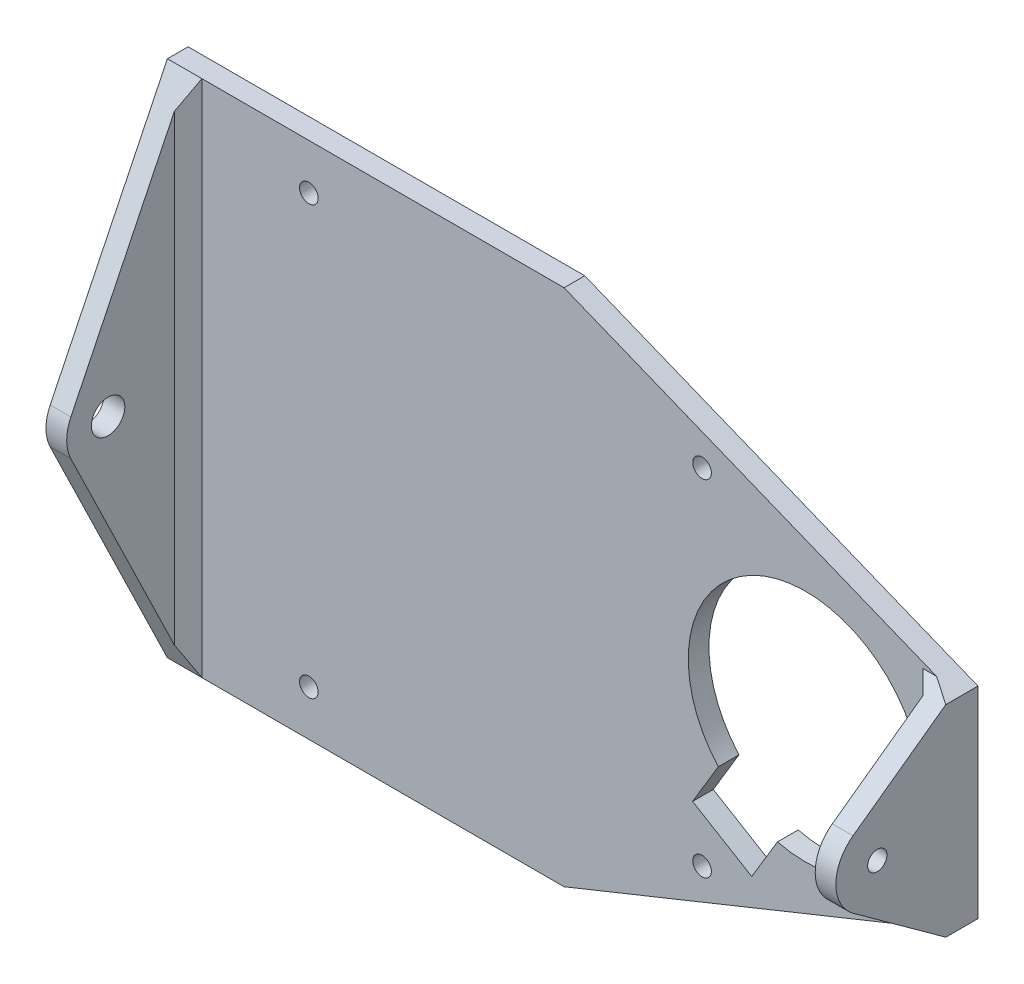
SolidWorks part; units mm, degrees
material "PET 90%"
ref_plane "Front Plane" through (0, 0, 0) normal (0, 0, 1) x (1, 0, 0)
ref_plane "Top Plane" through (0, 0, 0) normal (0, 1, 0) x (1, 0, 0)
ref_plane "Right Plane" through (0, 0, 0) normal (1, 0, 0) x (0, 0, -1)
sketch "Sketch1" plane through (0, 0, 0) normal (0, 0, 1) x (1, 0, 0)
  line L0 (-42.5, 37.6) -> (-42.5, -37.6)
  line L1 (-42.5, -37.6) -> (72, -37.6)
  line L2 (72, -37.6) -> (72, 37.6)
  line L3 (72, 37.6) -> (-42.5, 37.6)
  line L4 (0, 0) -> (-35.5, 0) construction
  line L5 (-35.5, 0) -> (-42.5, 0) construction
  line L6 (0, 0) -> (66, 0) construction
  line L7 (66, 0) -> (72, 0) construction
  line L8 (-22, 31) -> (-22, 32.6) construction
  line L9 (-22, 32.6) -> (-22, 37.6) construction
  line L10 (45.4594, -15.3422) -> (41.858, -21.3447) construction
  line L11 (34.998, -17.2287) -> (38.5995, -11.2262) construction
  line L12 (41.858, -21.3447) -> (34.998, -17.2287) construction
  line L13 (45.4594, -15.3422) -> (41.858, -21.3447) construction
  line L14 (34.998, -17.2287) -> (38.5995, -11.2262) construction
  line L15 (41.858, -21.3447) -> (34.998, -17.2287) construction
  circle A0 centre (-22, 31) radius 1.6 construction
  circle A1 centre (35, 25) radius 1.6 construction
  circle A2 centre (35, -25) radius 1.6 construction
  circle A3 centre (-22, -31) radius 1.6 construction
  circle A4 centre (-22, 31) radius 1.6 construction
  circle A5 centre (35, 25) radius 1.6 construction
  circle A6 centre (35, -25) radius 1.6 construction
  circle A7 centre (-22, -31) radius 1.6 construction
  arc A8 (-25.36, 24.8419) -> (-25.36, -24.8419) centre (0, 0) ccw construction
  arc A9 (-25.36, 24.8419) -> (-25.36, -24.8419) centre (0, 0) ccw construction
  arc A14 (45.4594, -15.3422) -> (38.5995, -11.2262) centre (50, 0) ccw construction
  arc A15 (45.4594, -15.3422) -> (38.5995, -11.2262) centre (50, 0) ccw construction
  dimension "D1" = 7
  dimension "D3" = 5
  dimension "D2" = 6
extrude "Boss-Extrude1" add sketch "Sketch1" along normal blind 3
ref_plane "Plane1" through (0, 0, 14.6) normal (0, 0, 1) x (1, 0, 0)
sketch "Sketch3" plane through (0, 0, 0) normal (0, 0, 1) x (1, 0, 0)
  line L0 (38.428, -19.2867) -> (50, 0) construction
  line L1 (41.858, -21.3447) -> (34.998, -17.2287) construction
  line L2 (37.353, -11.3601) -> (33.626, -17.5717)
  line L3 (33.626, -17.5717) -> (42.201, -22.7166)
  line L4 (42.201, -22.7166) -> (45.9279, -16.5051)
  line L5 (34.998, -17.2287) -> (38.5995, -11.2262) construction
  line L6 (15, -37.6) -> (72, -14.6)
  line L7 (45.4594, -15.3422) -> (41.858, -21.3447) construction
  line L8 (-42.5, -37.6) -> (72, -37.6) construction
  line L9 (72, -37.6) -> (72, 37.6) construction
  line L10 (15, 37.6) -> (72, 14.6)
  line L11 (72, 37.6) -> (-42.5, 37.6) construction
  line L12 (0, 0) -> (-42.5, 0) construction
  line L13 (-42.5, 37.6) -> (-42.5, -37.6) construction
  line L14 (15, -37.6) -> (72, -37.6)
  line L15 (72, -37.6) -> (72, -14.6)
  line L16 (72, 37.6) -> (15, 37.6)
  line L17 (72, 14.6) -> (72, 37.6)
  arc A2 (45.9279, -16.5051) -> (37.353, -11.3601) centre (50, 0) ccw
  arc A3 (45.4594, -15.3422) -> (38.5995, -11.2262) centre (50, 0) ccw construction
  circle A5 centre (35, 25) radius 1.35
  circle A6 centre (-22, 31) radius 1.35
  circle A7 centre (-22, -31) radius 1.35
  circle A8 centre (35, -25) radius 1.35
  dimension "D1" = 1
  dimension "D4" = 2.7
  dimension "D2" = 1
  dimension "D3" = 1
  dimension "D5" = 57
  dimension "D6" = 23
extrude "Cut-Extrude1" cut sketch "Sketch3" along normal up to next
sketch "Sketch5" plane through (0, 0, 3) normal (0, 0, 1) x (1, 0, 0)
  line L0 (72, -14.6) -> (15, -37.6) construction
  line L1 (72, -14.6) -> (69, -15.8105)
  line L2 (72, -14.6) -> (72, 14.6) construction
  line L3 (72, -14.6) -> (72, 14.6)
  line L4 (15, 37.6) -> (72, 14.6) construction
  line L5 (69, 15.8105) -> (72, 14.6)
  line L6 (69, 15.8105) -> (69, -15.8105)
  line L7 (-42.5, 37.6) -> (-42.5, -37.6) construction
  line L8 (-42.5, 37.6) -> (-42.5, -37.6)
  line L9 (-39.5, 37.6) -> (-39.5, -37.6)
  line L10 (15, 37.6) -> (-42.5, 37.6) construction
  line L11 (-42.5, -37.6) -> (15, -37.6) construction
  line L12 (-42.5, -37.6) -> (-39.5, -37.6)
  line L13 (-39.5, 37.6) -> (-42.5, 37.6)
  dimension "D1" = 3
  dimension "D2" = 3
extrude "Boss-Extrude3" add sketch "Sketch5" along normal offset from surface (17.6 mm away) 6 up to plane "Plane1" offset beyond the face yes
ref_axis "Rotation" through (-22.5499, 0, 14.6) along (1, 0, 0)
sketch "Sketch6" plane through (-42.5, 0, 0) normal (-1, 0, 0) x (0, 0, 1)
  line L1 (20.6, 37.6) -> (20.6, -37.6) construction
  line L2 (3, 37.6) -> (19.9966, 2.6224)
  line L5 (20.6, 37.6) -> (20.6, 0)
  line L8 (0, 0) -> (20.6, 0) construction
  line L9 (3, 37.6) -> (0, 37.6) construction
  line L10 (3, 37.6) -> (0, 37.6) construction
  line L11 (20.6, 37.6) -> (3, 37.6)
  arc A0 (20.6, 0) -> (19.9966, 2.6224) centre (14.6, 0) ccw
extrude "Cut-Extrude2" cut sketch "Sketch6" against normal up to next
sketch "Sketch7" plane through (-42.5, 0, 0) normal (-1, 0, 0) x (0, 0, 1)
  line L1 (20.6, 0) -> (20.6, -37.6)
  line L2 (19.9966, -2.6224) -> (3, -37.6)
  line L5 (3, -37.6) -> (0, -37.6) construction
  line L6 (3, -37.6) -> (0, -37.6) construction
  line L7 (20.6, -37.6) -> (3, -37.6)
  arc A0 (19.9966, -2.6224) -> (20.6, 0) centre (14.6, 0) ccw
extrude "Cut-Extrude3" cut sketch "Sketch7" against normal up to next
sketch "Sketch8" plane through (69, 0, 0) normal (-1, 0, 0) x (0, 0, 1)
  line L0 (18.1196, 4.8593) -> (3, 15.8105)
  line L1 (20.6, 15.8105) -> (3, 15.8105) construction
  line L2 (20.6, 15.8105) -> (3, 15.8105)
  line L4 (20.6, 15.8105) -> (20.6, -15.8105) construction
  line L5 (20.6, 15.8105) -> (20.6, 0)
  arc A0 (20.6, 0) -> (18.1196, 4.8593) centre (14.6, 0) ccw
extrude "Cut-Extrude4" cut sketch "Sketch8" against normal up to next
sketch "Sketch9" plane through (69, 0, 0) normal (-1, 0, 0) x (0, 0, 1)
  line L0 (20.6, 0) -> (20.6, -15.8105) construction
  line L1 (18.1196, -4.8593) -> (3, -15.8105)
  line L2 (20.6, -15.8105) -> (3, -15.8105) construction
  line L3 (20.6, -15.8105) -> (3, -15.8105)
  line L4 (20.6, 0) -> (20.6, -15.8105)
  arc A0 (18.1196, -4.8593) -> (20.6, 0) centre (14.6, 0) ccw
extrude "Cut-Extrude5" cut sketch "Sketch9" against normal up to next
sketch "Sketch10" plane through (-42.5, 0, 0) normal (-1, 0, 0) x (0, 0, 1)
  circle A0 centre (14.6, 0) radius 2.425
  dimension "D1" = 4.85
extrude "Cut-Extrude6" cut sketch "Sketch10" against normal up to next
sketch "Sketch11" plane through (72, 0, 0) normal (1, 0, 0) x (0, 0, -1)
  circle A0 centre (-14.6, 0) radius 1.4
  dimension "D1" = 2.8
extrude "Cut-Extrude7" cut sketch "Sketch11" against normal up to next
chamfer "Chamfer1" distance 2 angle 45 2 edges at (69, 0, 3) (-39.5, 0, 3)
equation "\"s\"=2.1653"
